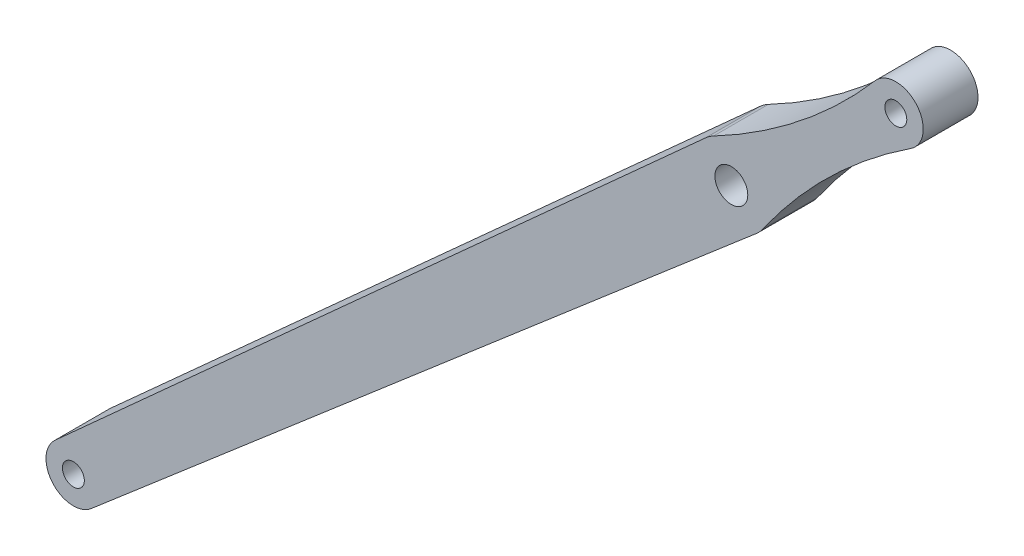
SolidWorks part; units mm, degrees
ref_plane "Front Plane" through (0, 0, 0) normal (0, 0, 1) x (1, 0, 0)
ref_plane "Top Plane" through (0, 0, 0) normal (0, 1, 0) x (1, 0, 0)
ref_plane "Right Plane" through (0, 0, 0) normal (1, 0, 0) x (0, 0, -1)
sketch "Sketch1" plane through (0, 0, 0) normal (0, 0, 1) x (1, 0, 0)
  line L0 (-134.5572, 125.7696) -> (-253.3267, 18.5791)
  line L3 (-125.3087, 115.2608) -> (-246.7206, 11.0728)
  circle A2 centre (-129.8673, 120.573) radius 7
  circle A3 centre (-249.9767, 14.8672) radius 5
  circle A4 centre (-99.8399, 146.9994) radius 5
  arc A5 (-133.1183, 126.7723) -> (-103.6361, 150.2534) centre (-179.5612, 215.3333) ccw
  arc A6 (-97.0946, 142.8205) -> (-124.1313, 116.5607) centre (-42.1887, 59.2422) ccw
  circle A7 centre (-249.9767, 14.8672) radius 2 construction
  circle A8 centre (-249.9767, 14.8672) radius 2
  circle A9 centre (-129.8673, 120.573) radius 3 construction
  circle A10 centre (-129.8673, 120.573) radius 3
  circle A11 centre (-99.8399, 146.9994) radius 2 construction
  circle A12 centre (-99.8399, 146.9994) radius 2
  dimension "D1" = 14
  dimension "D2" = 10
  dimension "D3" = 10
  dimension "D4" = 100
  dimension "D5" = 100
extrude "Boss-Extrude1" add sketch "Sketch1" along normal blind 5 and the other way blind 5 contours A3 L3 A2 L0 | A3 | A2 | A6 A4 A5 A2 | A4 region at (-187.5652, 69.7943, 0) region at (-133.7561, 126.1537, 0) region at (-248.0032, 19.3069, 0) region at (-114.7411, 133.8852, 0) region at (-98.1542, 151.5562, 0)
